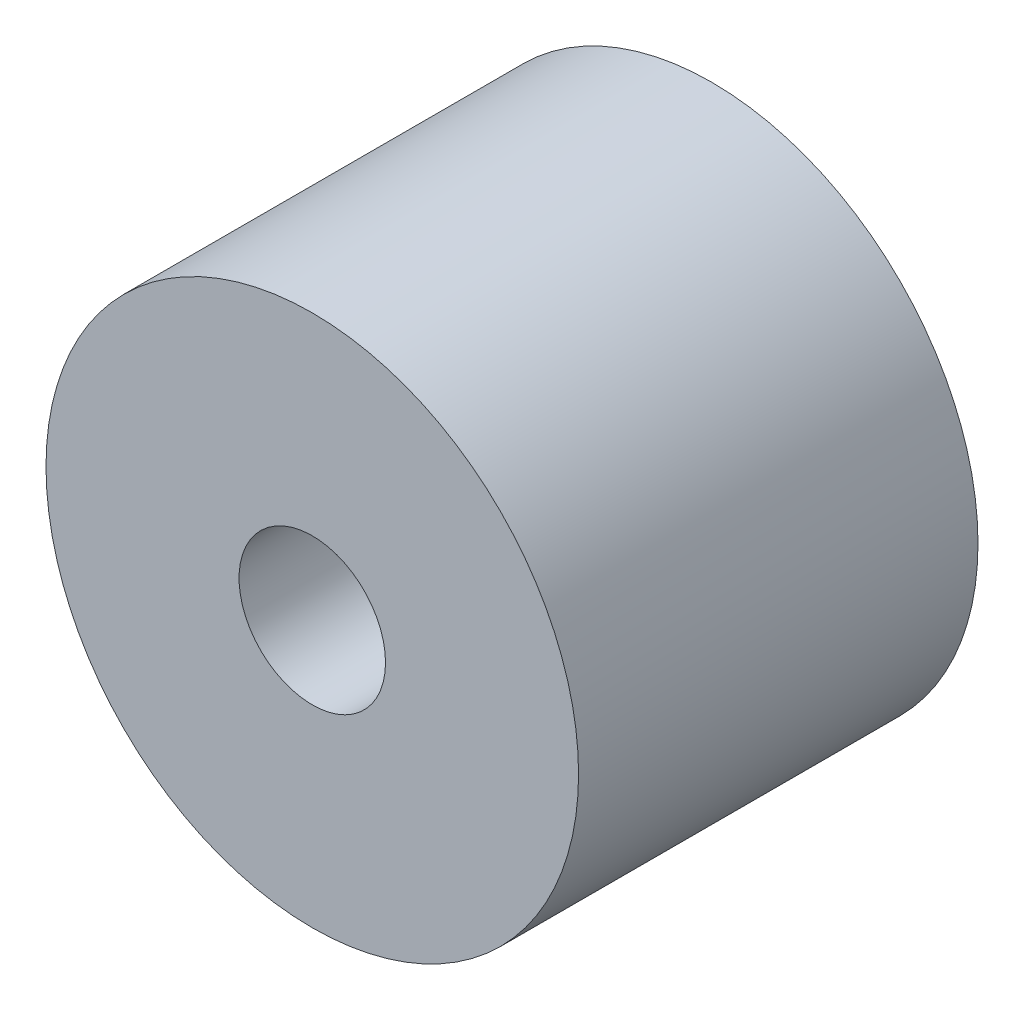
SolidWorks part; units mm, degrees
material "ABS"
ref_plane "Front Plane" through (0, 0, 0) normal (0, 0, 1) x (1, 0, 0)
ref_plane "Top Plane" through (0, 0, 0) normal (0, 1, 0) x (1, 0, 0)
ref_plane "Right Plane" through (0, 0, 0) normal (1, 0, 0) x (0, 0, -1)
sketch "Sketch1" plane through (0, 0, 0) normal (0, 0, 1) x (1, 0, 0)
  circle A0 centre (0, 0) radius 2.75
  circle A1 centre (0, 0) radius 10
  dimension "D1" = 20
  dimension "D2" = 5.5
extrude "Boss-Extrude1" add sketch "Sketch1" along normal mid plane 15
ref_axis "Axis1" through (0, 0, 7.5) along (0, 0, -1)
